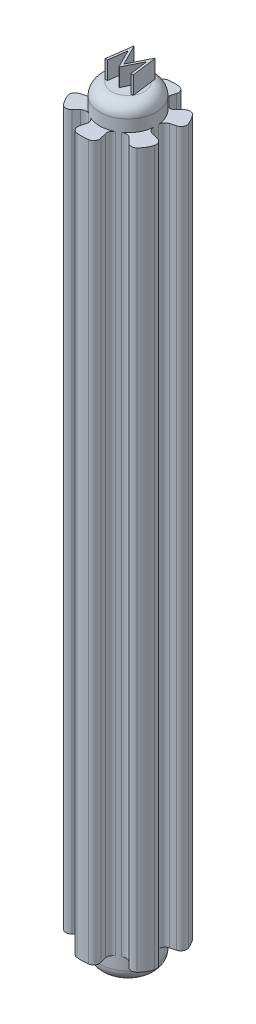
SolidWorks part; units mm, degrees
ref_plane "Front Plane" through (0, 0, 0) normal (0, 0, 1) x (1, 0, 0)
ref_plane "Top Plane" through (0, 0, 0) normal (0, 1, 0) x (1, 0, 0)
ref_plane "Right Plane" through (0, 0, 0) normal (1, 0, 0) x (0, 0, -1)
sketch "Sketch2" plane through (0, 0, 0) normal (0, 1, 0) x (1, 0, 0)
  line L0 (0, 0) -> (0.0739, 0)
  line L2 (2.3008, -0.5891) -> (3.7752, -0.9786)
  line L3 (0.0739, 0) -> (0.1042, -0.0303)
  line L4 (0, 0) -> (0.0858, -0.0446)
  line L5 (1.6802, 1.6786) -> (2.7413, 2.7388)
  line L6 (-1.6794, 1.6794) -> (-2.74, 2.74)
  line L8 (0.6147, 2.2941) -> (1.0029, 3.743)
  line L9 (-0.6147, 2.2941) -> (-1.0029, 3.743)
  line L10 (2.2941, 0.6147) -> (3.743, 1.0029)
  line L11 (0, 0) -> (0.1042, -0.0303)
  line L12 (-2.2941, 0.6147) -> (-3.743, 1.0029)
  line L13 (0.0739, 0) -> (0.0858, -0.0446)
  line L14 (-0.6147, -2.2941) -> (-1.0029, -3.743)
  line L15 (-2.2941, -0.6147) -> (-3.743, -1.0029)
  line L16 (-1.6794, -1.6794) -> (-2.74, -2.74)
  line L17 (0.6814, -2.2752) -> (1.0684, -3.7248)
  line L18 (1.7145, -1.6435) -> (2.7672, -2.6981)
  arc A0 (-2.2941, 0.6147) -> (-2.2941, -0.6147) centre (0, 0) ccw
  arc A1 (-2.74, 2.74) -> (-3.743, 1.0029) centre (0, 0) ccw
  arc A2 (1.0029, 3.743) -> (-1.0029, 3.743) centre (0, 0) ccw
  arc A3 (3.743, 1.0029) -> (2.7413, 2.7388) centre (0, 0) ccw
  arc A5 (-1.0029, -3.743) -> (1.0684, -3.7248) centre (0, 0) ccw
  arc A6 (-3.743, -1.0029) -> (-2.74, -2.74) centre (0, 0) ccw
  arc A7 (-2.74, 2.74) -> (-3.743, 1.0029) centre (0, 0) ccw
  arc A8 (1.0029, 3.743) -> (-1.0029, 3.743) centre (0, 0) ccw
  arc A9 (3.743, 1.0029) -> (2.7413, 2.7388) centre (0, 0) ccw
  arc A10 (-3.743, -1.0029) -> (-2.74, -2.74) centre (0, 0) ccw
  arc A11 (-1.0029, -3.743) -> (1.0684, -3.7248) centre (0, 0) ccw
  arc A12 (2.7672, -2.6981) -> (3.7752, -0.9786) centre (1.7753, -0.9614) ccw
  arc A13 (-0.6147, 2.2941) -> (-1.6794, 1.6794) centre (0, 0) ccw
  arc A14 (1.6802, 1.6786) -> (0.6147, 2.2941) centre (0, 0) ccw
  arc A15 (2.3008, -0.5891) -> (2.2941, 0.6147) centre (0, 0) ccw
  arc A16 (0.6814, -2.2752) -> (1.7145, -1.6435) centre (0, 0) ccw
  arc A17 (-1.6794, -1.6794) -> (-0.6147, -2.2941) centre (0, 0) ccw
  dimension "D1" = 3.875
  dimension "D2" = 2.375
extrude "Boss-Extrude1" add sketch "Sketch2" along normal blind 60 contours L16 A17 L14 A5 L17 A16 L18 A12 L2 A15 L10 A3 L5 A14 L8 A2 L9 A13 L6 A1 L12 A0 L15 A6 L11 L13 L4 L0 L3 region at (0.0225, 0, 0.0171)
sketch "Sketch4" plane through (0, 60, 0) normal (0, 1, 0) x (1, 0, 0)
  circle A0 centre (0, 0) radius 2.375
  dimension "D1" = 4.75
extrude "Boss-Extrude3" add sketch "Sketch4" along normal blind 2
fillet "Fillet1" radius 0.5 24 edges at (-2.74, 30, -2.74) (-1.6794, 30, -1.6794) (-0.6147, 30, -2.2941) (-1.0029, 30, -3.743) (1.0029, 30, -3.743) (0.6147, 30, -2.2941) (1.6802, 30, -1.6786) (2.7413, 30, -2.7388) (3.743, 30, -1.0029) (2.2941, 30, -0.6147) (2.3008, 30, 0.5891) (3.7752, 30, 0.9786) (2.7672, 30, 2.6981) (1.7145, 30, 1.6435) (0.6814, 30, 2.2752) (-1.6794, 30, 1.6794) (-2.2941, 30, 0.6147) (-2.2941, 30, -0.6147) (-0.6147, 30, 2.2941) (-3.743, 30, -1.0029) (-3.743, 30, 1.0029) (-2.74, 30, 2.74) (-1.0029, 30, 3.743) (1.0684, 30, 3.7248)
sketch "Sketch5" plane through (0, 62, 0) normal (0, 1, 0) x (1, 0, 0)
  text T0 "M" font "Century Gothic" height in points 8
extrude "Boss-Extrude4" add sketch "Sketch5" along normal blind 1.5
sketch "Sketch6" plane through (0, 0, 0) normal (0, -1, 0) x (1, 0, 0)
  circle A0 centre (0, 0) radius 2.375
  dimension "D1" = 4.75
extrude "Boss-Extrude5" add sketch "Sketch6" along normal blind 2
fillet "Fillet2" radius 1 2 edges at (0, 62, 2.375) (0, -2, -2.375)
